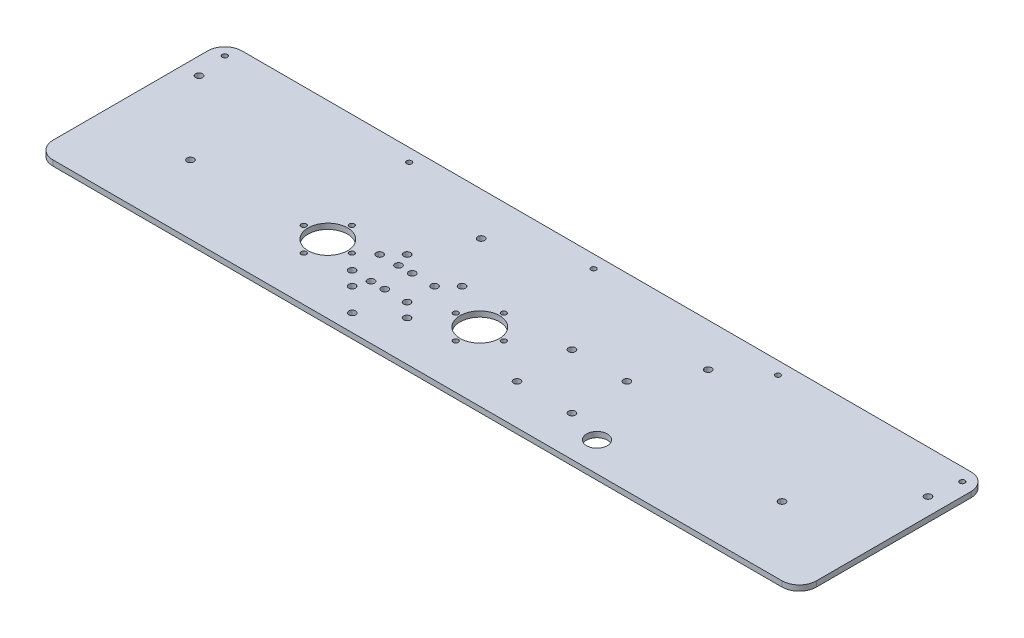
SolidWorks part; units mm, degrees
ref_plane "Front" through (0, 0, 0) normal (0, 0, 1) x (1, 0, 0)
ref_plane "Top" through (0, 0, 0) normal (0, 1, 0) x (1, 0, 0)
ref_plane "Right" through (0, 0, 0) normal (1, 0, 0) x (0, 0, -1)
sketch "Sketch1" plane through (0, 0, 0) normal (0, 1, 0) x (1, 0, 0)
  line L0 (-26.7996, 0) -> (-26.7996, 40)
  line L1 (-26.7996, 0) -> (417.7004, 0)
  line L2 (-26.7996, 0) -> (-26.7996, 110)
  line L3 (-26.7996, 110) -> (417.7004, 110)
  line L4 (417.7004, 0) -> (417.7004, 110)
  line L5 (-26.7996, 40) -> (23.2004, 40)
  line L6 (417.7004, 0) -> (417.7004, 40)
  line L7 (417.7004, 40) -> (367.7004, 40)
  line L8 (23.2004, 40) -> (103.2004, 40)
  line L9 (367.7004, 40) -> (191.7004, 40)
  line L10 (-26.7996, 110) -> (-26.7996, 85)
  line L11 (-26.7996, 85) -> (417.7004, 85)
  line L12 (-26.7996, 85) -> (-16.7996, 85)
  line L13 (417.7004, 85) -> (407.7004, 85)
  line L14 (103.2004, 40) -> (191.7004, 40)
  line L15 (147.4504, 40) -> (147.4504, 85)
  line L16 (279.7004, 40) -> (279.7004, 85)
  line L17 (147.4504, 40) -> (147.4504, 10)
  line L18 (-26.7996, 110) -> (-26.7996, 102.5)
  line L19 (-26.7996, 102.5) -> (417.7004, 102.5)
  line L20 (-26.7996, 102.5) -> (-19.2996, 102.5)
  line L21 (417.7004, 102.5) -> (410.2004, 102.5)
  line L22 (195.4504, 102.5) -> (410.2004, 102.5)
  line L23 (-19.2996, 102.5) -> (195.4504, 102.5)
  line L24 (417.7004, 0) -> (417.7004, 17.2282)
  line L25 (417.7004, 17.2282) -> (282.7004, 17.2282)
  circle A10 centre (367.7004, 40) radius 2
  circle A11 centre (23.2004, 40) radius 2
  circle A12 centre (103.2004, 40) radius 11.5
  circle A13 centre (103.2004, 40) radius 14
  circle A15 centre (103.2004, 54) radius 1.5
  circle A16 centre (89.2004, 40) radius 1.5
  circle A17 centre (103.2004, 26) radius 1.5
  circle A18 centre (117.2004, 40) radius 1.5
  circle A19 centre (191.7004, 40) radius 11.5
  circle A20 centre (191.7004, 40) radius 14
  circle A21 centre (191.7004, 26) radius 1.5
  circle A22 centre (205.7004, 40) radius 1.5
  circle A23 centre (191.7004, 54) radius 1.5
  circle A24 centre (177.7004, 40) radius 1.5
  circle A25 centre (-16.7996, 85) radius 2
  circle A26 centre (407.7004, 85) radius 2
  circle A27 centre (147.4504, 85) radius 2
  circle A28 centre (279.7004, 85) radius 2
  circle A29 centre (147.4504, 10) radius 2
  circle A30 centre (195.4504, 102.5) radius 1.5
  circle A31 centre (-19.2996, 102.5) radius 1.5
  circle A32 centre (410.2004, 102.5) radius 1.5
  circle A33 centre (302.8254, 102.5) radius 1.5
  circle A34 centre (88.0754, 102.5) radius 1.5
  circle A35 centre (282.7004, 17.2282) radius 6
  dimension "D3" = 40
  dimension "D7" = 80
  dimension "D8" = 176
  dimension "D9" = 25
  dimension "D11" = 10
  dimension "D12" = 30
  dimension "D13" = 7.5
  dimension "D14" = 7.5
  dimension "D16" = 17.2282
  dimension "D1" = 110
  dimension "D2" = 444.5
  dimension "D4" = 50
  dimension "D5" = 40
  dimension "D6" = 50
  dimension "D10" = 10
  dimension "D15" = 7.5
  dimension "D17" = 135
extrude "Boss-Extrude1" add sketch "Sketch1" along normal blind 3.175 contours A18 L14 A12 L8 A16 A13 A17 | A18 A13 A15 A16 L8 A12 L14 | A24 L14 A19 L9 A22 A20 A23 | A24 A20 A21 A22 L9 A19 L14 | A29 L14 A18 A13 A17 A16 L8 A11 L5 L0 L1 L4 L7 A10 L9 A22 A20 A21 A24 | A28 L11 A27 L15 L14 A24 A20 A23 A22 L9 L16 | A27 L11 A25 L2 L5 A11 L8 A16 A13 A15 A18 L14 L15 | A28 L11 A26 L13 L4 L3 L2 A25 A27 | A28 L16 L9 A10 L7 L4 L13 A26 L11 | A34 L23 A30 L22 A33 A32 L21 L4 L3 L10 L19 A31 region at (196.684, 0, -19.4923) region at (58.5861, 0, -63.184) region at (195.421, 0, -93.7571) region at (195.4504, 0, -106.2666) region at (348.6559, 0, -62.489) region at (93.521, 0, -49.6794) region at (90.515, 0, -38.754) region at (214.7998, 0, -63.4004) region at (204.3858, 0, -41.246) region at (201.3798, 0, -30.3206)
fillet "Fillet1" radius 10 4 edges at (417.7004, 1.5875, -110) (417.7004, 1.5875, 0) (-26.7996, 1.5875, 0) (-26.7996, 1.5875, -110)
sketch "Sketch2" plane through (0, 3.175, 0) normal (0, 1, 0) x (1, 0, 0)
  line L0 (-26.7996, 55.4056) -> (36.2004, 55.4056)
  line L1 (-26.7996, 10) -> (-26.7996, 100) construction
  line L2 (36.2004, 55.4056) -> (76.2004, 55.4056)
  line L3 (-16.7996, 110) -> (407.7004, 110) construction
  line L4 (36.2004, 55.4056) -> (36.2004, 23.4056)
  line L5 (36.2004, 23.4056) -> (68.2004, 23.4056)
  line L6 (76.2004, 55.4056) -> (165.9504, 55.4056)
  line L7 (165.9504, 55.4056) -> (133.9504, 55.4056)
  line L8 (133.9504, 55.4056) -> (133.9504, 23.4056)
  line L9 (133.9504, 23.4056) -> (165.9504, 23.4056)
  line L10 (133.9504, 23.4056) -> (125.9504, 23.4056)
  line L11 (125.9504, 23.4056) -> (125.9504, 55.4056)
  line L12 (165.9504, 55.4056) -> (157.9504, 55.4056)
  line L13 (157.9504, 55.4056) -> (157.9504, 23.4056)
  line L14 (157.9504, 23.4056) -> (157.9504, 31.4056)
  line L15 (157.9504, 55.4056) -> (157.9504, 47.4056)
  line L16 (157.9504, 47.4056) -> (133.9504, 47.4056)
  circle A4 centre (133.9504, 55.4056) radius 2
  circle A5 centre (165.9504, 55.4056) radius 2
  circle A9 centre (133.9504, 23.4056) radius 2
  circle A10 centre (165.9504, 23.4056) radius 2
  circle A11 centre (157.9504, 31.4056) radius 2
  circle A12 centre (125.9504, 31.4056) radius 2
  circle A13 centre (125.9504, 47.4056) radius 2
  circle A14 centre (157.9504, 47.4056) radius 2
  dimension "D5" = 89.75
  dimension "D6" = 32
  dimension "D7" = 8
  dimension "D10" = 8
  dimension "D1" = 63
  dimension "D2" = 40
  dimension "D3" = 54.5944
  dimension "D4" = 32
  dimension "D8" = 8
  dimension "D9" = 8
extrude "Cut-Extrude1" cut sketch "Sketch2" against normal blind 10 contours A4 | A5 | A13 | A12 | A9 | A10 | A11 | A14
sketch "Sketch3" plane through (0, 0, 0) normal (0, -1, 0) x (1, 0, 0)
  line L0 (133.9504, -55.4056) -> (133.9504, -47.4056)
  line L1 (133.9504, -47.4056) -> (136.9504, -47.4056)
  line L2 (136.9504, -47.4056) -> (144.9504, -47.4056)
  line L3 (136.9504, -47.4056) -> (136.9504, -31.4056)
  line L4 (136.9504, -31.4056) -> (144.9504, -31.4056)
  line L5 (165.9504, -55.4056) -> (229.9504, -55.4056)
  line L6 (229.9504, -55.4056) -> (261.9504, -55.4056)
  line L7 (261.9504, -55.4056) -> (261.9504, -23.4056)
  line L8 (261.9504, -23.4056) -> (229.9504, -23.4056)
  circle A0 centre (144.9504, -47.4056) radius 2
  circle A1 centre (136.9504, -47.4056) radius 2
  circle A2 centre (144.9504, -31.4056) radius 2
  circle A3 centre (136.9504, -31.4056) radius 2
  circle A4 centre (261.9504, -55.4056) radius 2
  circle A5 centre (229.9504, -55.4056) radius 2
  circle A6 centre (261.9504, -23.4056) radius 2
  circle A7 centre (229.9504, -23.4056) radius 2
  dimension "D3" = 8
  dimension "D5" = 64
  dimension "D7" = 32
  dimension "D1" = 3
  dimension "D2" = 8
  dimension "D4" = 16
  dimension "D6" = 32
extrude "Cut-Extrude2" cut sketch "Sketch3" against normal blind 10 contours L2 A1 L1 | L1 A1 L2 | A2 | L4 A3 L3 | L3 A1 L1 | L3 A3 L4 | A0 | A4 | A6 | A7 | A5 region at (136.1016, 0, -46.5568) region at (144.9504, 0, -29.4622) region at (136.6675, 0, -31.1227) region at (137.7992, 0, -32.2544) region at (136.9504, 0, -48.2544) region at (137.7992, 0, -46.5568)
sketch "Sketch4" plane through (0, 3.175, 0) normal (0, 1, 0) x (1, 0, 0)
  circle A0 centre (21.5907, 102.5) radius 1.5
  circle A1 centre (5.6648, 58.9528) radius 1.5
  circle A2 centre (-10.261, 15.4056) radius 1.5
  circle A3 centre (47.3504, 50.9056) radius 2
  circle A4 centre (115.6708, 102.5) radius 1.5
  circle A5 centre (145.6708, 102.5) radius 1.5
  circle A6 centre (175.6708, 102.5) radius 1.5
  circle A7 centre (47.3504, 95.9056) radius 2
  circle A8 centre (21.5907, 15.4056) radius 1.5
  circle A9 centre (47.3504, 28.4056) radius 2
  circle A10 centre (208.9504, 80.8056) radius 2
  circle A11 centre (184.9504, 80.8056) radius 2
  circle A12 centre (109.9504, 80.8056) radius 2
  circle A13 centre (85.9504, 80.8056) radius 2
extrude "Cut-Extrude3" [suppressed] cut sketch "Sketch4" against normal blind 6.35
sketch "Sketch5" [suppressed] plane through (0, 3.175, 0) normal (0, 1, 0) x (1, 0, 0)
  circle A0 centre (47.3504, 95.9056) radius 5
  circle A1 centre (47.3504, 50.9056) radius 5
  circle A2 centre (47.3504, 28.4056) radius 5
extrude "Cut-Extrude4" [suppressed] cut sketch "Sketch5" against normal blind 3.175
